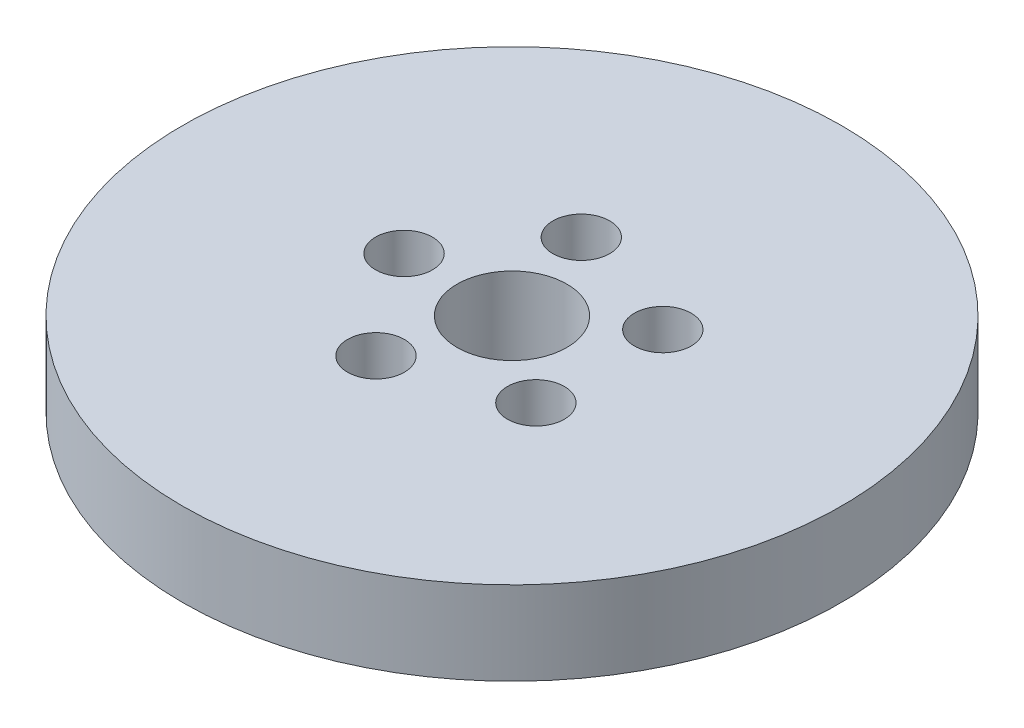
SolidWorks part; units mm, degrees
ref_plane "Front Plane" through (0, 0, 0) normal (0, 0, 1) x (1, 0, 0)
ref_plane "Top Plane" through (0, 0, 0) normal (0, 1, 0) x (1, 0, 0)
ref_plane "Right Plane" through (0, 0, 0) normal (1, 0, 0) x (0, 0, -1)
sketch "Sketch1" plane through (0, 0, 0) normal (0, 1, 0) x (1, 0, 0)
  circle A0 centre (0, 0) radius 75
  dimension "FLANGE_OD" = 150
extrude "Boss-Extrude1" add sketch "Sketch1" along normal blind 19
sketch "Sketch2" plane through (0, 0, 0) normal (0, 1, 0) x (1, 0, 0)
  circle A0 centre (0, 0) radius 12.5
  dimension "BORE_D" = 25
extrude "Cut-Extrude1" cut sketch "Sketch2" along normal through all
sketch "Sketch3" plane through (0, 19, 0) normal (0, 1, 0) x (1, 0, 0)
  circle A0 centre (0, 0) radius 24.569 construction
  circle A1 centre (-24.569, 0) radius 6.4725
  dimension "BOLT_D" = 12.945
  dimension "BOLT_PCD" = 49.138
extrude "Cut-Extrude2" cut sketch "Sketch3" against normal blind 18.2945
pattern_circular "CirPattern1" count 5 over 360 about axis through (0, 0, 0) along (0, 1, 0) of "Cut-Extrude2"
